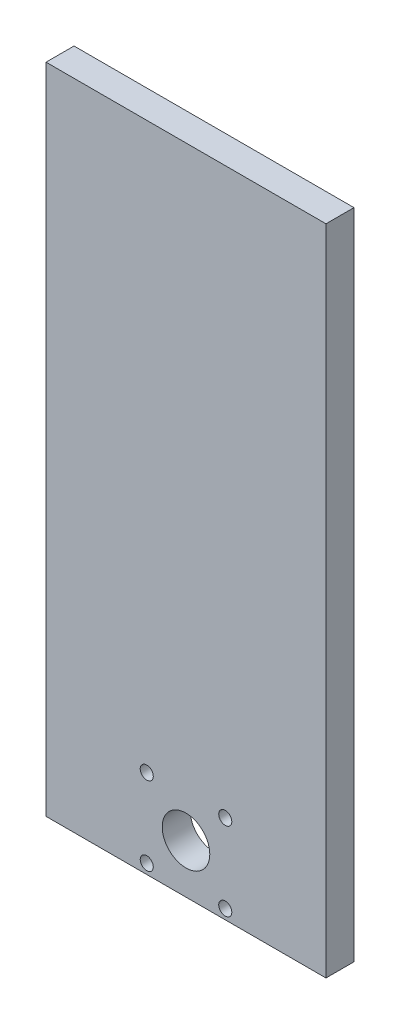
SolidWorks part; units mm, degrees
ref_plane "xy_plane" through (0, 0, 0) normal (0, 0, 1) x (1, 0, 0)
ref_plane "zx_plane" through (0, 0, 0) normal (0, 1, 0) x (1, 0, 0)
ref_plane "yz_plane" through (0, 0, 0) normal (1, 0, 0) x (0, 0, -1)
ref_axis "x_axis" through (-80.9, 0, 0) along (1, 0, 0)
ref_axis "y_axis" through (0, -50, 0) along (0, 1, 0)
ref_axis "z_axis" through (0, 0, -80.9) along (0, 0, 1)
ref_plane "xMid_plane" through (0, 0, 0) normal (1, 0, 0) x (0, 0, -1)
ref_plane "xMin_plane" through (-15, 0, 0) normal (1, 0, 0) x (0, 0, -1)
ref_plane "xMax_plane" through (15, 0, 0) normal (1, 0, 0) x (0, 0, -1)
ref_plane "yMid_plane" through (0, 0, 0) normal (0, 1, 0) x (1, 0, 0)
ref_plane "yMin_plane" through (0, -35, 0) normal (0, 1, 0) x (1, 0, 0)
ref_plane "yMax_plane" through (0, 35, 0) normal (0, 1, 0) x (1, 0, 0)
ref_plane "zMid_plane" through (0, 0, 0) normal (0, 0, 1) x (1, 0, 0)
ref_plane "zMin_plane" through (0, 0, -1.5) normal (0, 0, 1) x (1, 0, 0)
ref_plane "zMax_plane" through (0, 0, 1.5) normal (0, 0, 1) x (1, 0, 0)
sketch "projectionXy_sketch" plane through (0, 0, 0) normal (0, 0, 1) x (1, 0, 0)
  line L0 (55, 35) -> (-55, 35) construction
  line L1 (-15, 35) -> (15, 35)
  line L2 (-15, 35) -> (-15, -35)
  line L3 (-15, -35) -> (15, -35)
  line L4 (15, 35) -> (15, -35)
  line L5 (55, -35) -> (-55, -35) construction
  line L6 (15, -55) -> (15, 55) construction
  line L7 (-15, -55) -> (-15, 55) construction
extrude "mainBody_extrude" add sketch "projectionXy_sketch" along normal up to surface (1.5 mm away) from surface up to plane "zMax_plane" starting at plane "zMin_plane"
sketch "bore_sketch" plane through (0, 0, 0) normal (0, 0, 1) x (1, 0, 0)
  circle A0 centre (0, -29.7427) radius 2.55
  point P2 (0, 0)
  dimension "D1" = 5.1
extrude "bore_cut" cut sketch "bore_sketch" against normal through all both and the other way through all from surface starting at plane "zMid_plane"
sketch "postClearanceHoles_sketch" plane through (0, 0, 0) normal (0, 0, 1) x (1, 0, 0)
  circle A0 centre (4.2073, -25.5354) radius 0.7
  circle A1 centre (-4.2073, -25.5354) radius 0.7
  circle A2 centre (-4.2073, -33.95) radius 0.7
  circle A3 centre (4.2073, -33.95) radius 0.7
  point P8 (0, 0)
  point P10 (0, 0)
  point P12 (0, 0)
  point P14 (0, 0)
  dimension "D1" = 1.4
extrude "postClearanceHoles_cut" cut sketch "postClearanceHoles_sketch" against normal through all both and the other way through all from surface starting at plane "zMid_plane"
equation "\"D1@xMin_plane\"= \"externalParameters.this.extentX\" / 2"
equation "\"D1@xMax_plane\" = \"externalParameters.this.extentX\" / 2"
equation "\"D1@yMin_plane\" = \"externalParameters.this.extentY\" / 2"
equation "\"D1@yMax_plane\" = \"externalParameters.this.extentY\" / 2"
equation "\"D1@zMin_plane\" = \"externalParameters.this.extentZ\" / 2"
equation "\"D1@zMax_plane\" = \"externalParameters.this.extentZ\" / 2"
equation "\"D1@bore_sketch\" = \"externalParameters.this.bore.diameter\""
equation "\"D1@postClearanceHoles_sketch\" = \"externalParameters.this.postClearanceHole.diameter\""
